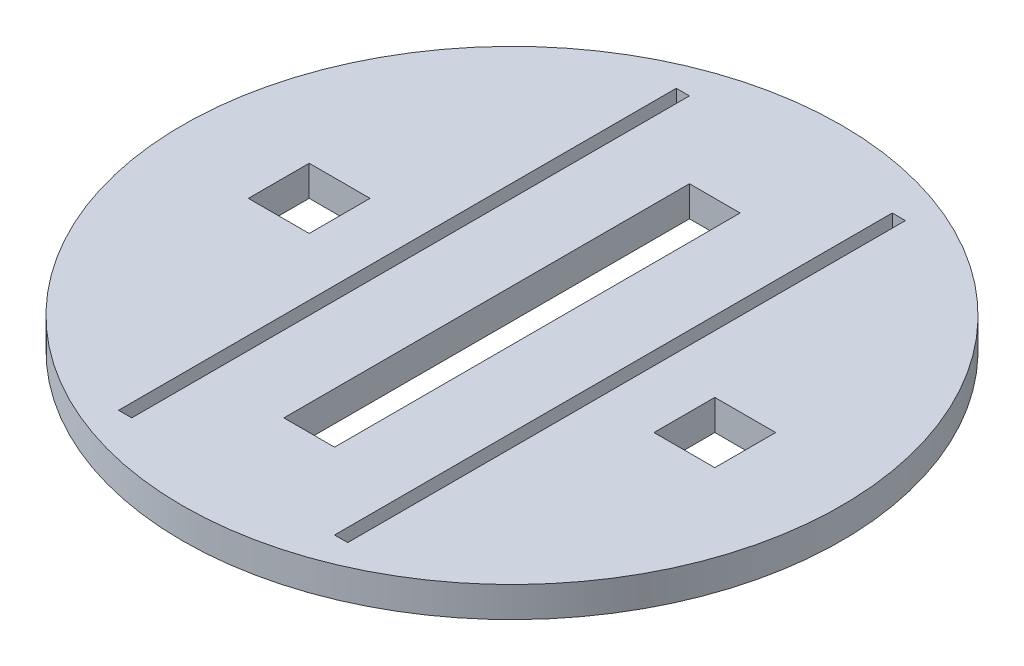
SolidWorks part; units mm, degrees
material "Mahogany"
ref_plane "Front Plane" through (0, 0, 0) normal (0, 0, 1) x (1, 0, 0)
ref_plane "Top Plane" through (0, 0, 0) normal (0, 1, 0) x (1, 0, 0)
ref_plane "Right Plane" through (0, 0, 0) normal (1, 0, 0) x (0, 0, -1)
sketch "Sketch1" plane through (0, 0, 0) normal (0, 1, 0) x (1, 0, 0)
  circle A0 centre (0, 0) radius 32.5
  dimension "D1" = 65
extrude "Boss-Extrude1" add sketch "Sketch1" along normal blind 3
sketch "Sketch2" plane through (0, 0, 0) normal (0, 0, 1) x (1, 0, 0)
  line L0 (-32.5, 0) -> (32.5, 0) construction
  line L1 (-10, 3.3643) -> (-11.3, 3.3643)
  line L2 (-10, 3.3643) -> (-10, -3.3643)
  line L3 (-10, -3.3643) -> (-11.3, -3.3643)
  line L4 (-11.3, 3.3643) -> (-11.3, -3.3643)
  line L5 (-10, 3.3643) -> (-11.3, -3.3643) construction
  line L6 (-10, -3.3643) -> (-11.3, 3.3643) construction
  line L7 (0, -2.9347) -> (0, 9.2473) construction
  line L8 (10, -3.3643) -> (11.3, 3.3643) construction
  line L9 (10, 3.3643) -> (11.3, -3.3643) construction
  line L10 (11.3, 3.3643) -> (11.3, -3.3643)
  line L11 (10, -3.3643) -> (11.3, -3.3643)
  line L12 (10, 3.3643) -> (10, -3.3643)
  line L13 (10, 3.3643) -> (11.3, 3.3643)
  point P0 (-10.65, 0)
  point P10 (10.65, 0)
  dimension "D1" = 10
  dimension "D2" = 1.3
extrude "Cut-Extrude1" cut sketch "Sketch2" along normal blind 27.5 and the other way blind 27.5
sketch "Sketch3" plane through (0, 0, 0) normal (0, 1, 0) x (1, 0, 0)
  line L1 (-17, 3) -> (-23, 3)
  line L2 (-17, 3) -> (-17, -3)
  line L3 (-17, -3) -> (-23, -3)
  line L4 (-23, 3) -> (-23, -3)
  line L5 (-17, 3) -> (-23, -3) construction
  line L6 (-17, -3) -> (-23, 3) construction
  line L10 (17, -3) -> (23, -3)
  line L11 (17, -3) -> (17, 3)
  line L12 (17, 3) -> (23, 3)
  line L13 (23, -3) -> (23, 3)
  line L18 (-3, -17) -> (-3, -23) [skipped]
  line L19 (-3, -17) -> (3, -17) [skipped]
  line L20 (3, -17) -> (3, -23) [skipped]
  line L21 (-3, -23) -> (3, -23) [skipped]
  line L22 (3, 17) -> (-3, 17) [skipped]
  line L23 (3, 17) -> (3, 23) [skipped]
  line L24 (3, 23) -> (-3, 23) [skipped]
  line L25 (-3, 17) -> (-3, 23) [skipped]
  circle A0 centre (0, 0) radius 20 construction
  point P3 (-20, 0)
  point P23 (0, 0)
  dimension "D1" = 40
  dimension "D4" = 4
  dimension "D2" = 6
  dimension "D3" = 6
extrude "Cut-Extrude2" cut sketch "Sketch3" along normal blind 10
sketch "Sketch4" plane through (0, 0, 0) normal (0, -1, 0) x (1, 0, 0)
  line L1 (2.5, -20) -> (-2.5, -20)
  line L2 (2.5, -20) -> (2.5, 20)
  line L3 (2.5, 20) -> (-2.5, 20)
  line L4 (-2.5, -20) -> (-2.5, 20)
  line L5 (2.5, -20) -> (-2.5, 20) construction
  line L6 (2.5, 20) -> (-2.5, -20) construction
  point P0 (0, 0)
  dimension "D1" = 5
  dimension "D2" = 40
extrude "Cut-Extrude3" cut sketch "Sketch4" against normal blind 10
